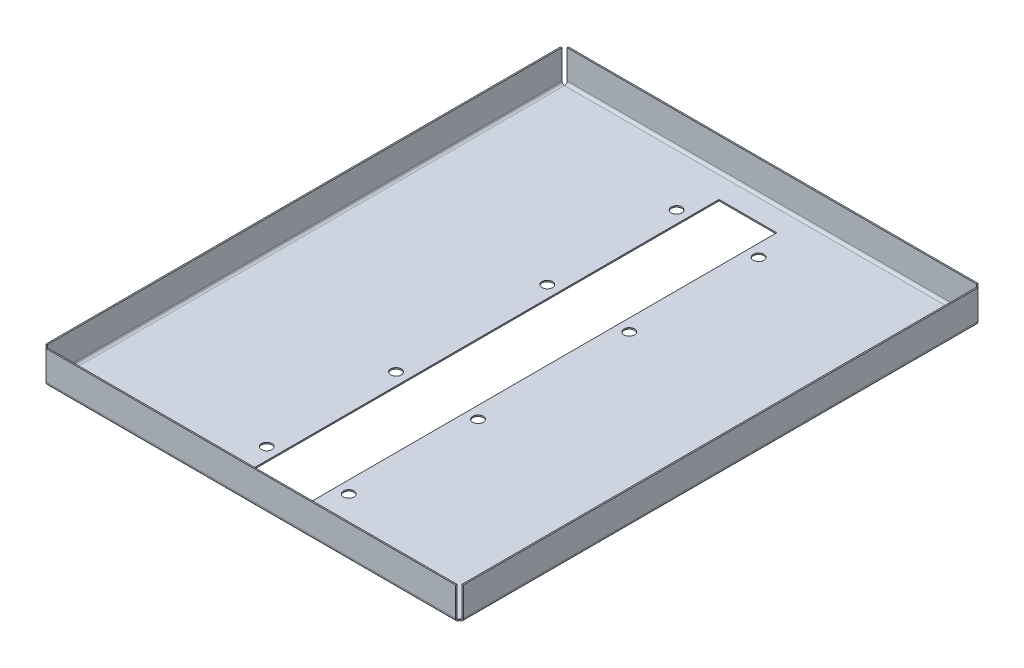
SolidWorks part; units mm, degrees
note: The reader was unsure of these and kept them because the rebuilt part matched: flange length of "Edge-Flange1", "Edge-Flange2", "Edge-Flange3", "Edge-Flange4".
ref_plane "Front Plane" through (0, 0, 0) normal (0, 0, 1) x (1, 0, 0)
ref_plane "Top Plane" through (0, 0, 0) normal (0, 1, 0) x (1, 0, 0)
ref_plane "Right Plane" through (0, 0, 0) normal (1, 0, 0) x (0, 0, -1)
sketch "Sketch1" plane through (0, 0, 0) normal (0, 1, 0) x (1, 0, 0)
  line L1 (0, 0) -> (156, 0)
  line L2 (0, 0) -> (0, -196)
  line L3 (0, -196) -> (156, -196)
  line L4 (156, 0) -> (156, -196)
base flange "Base-Flange1" sketch "Sketch1" thickness 0.5 reverse thickness direction no parameters "D1"=20
edge flange "Edge-Flange1" sketch "Sketch4" flange angle 90 flange length 12 flange position bend outside bend radius 1 thickness 0.5 parameters "D6"=10
sketch "Sketch4" plane through (0, 0, 0) normal (1, 0, 0) x (0, 0, -1)
  line L1 (0, 0) -> (-196, 0) construction
  line L2 (-196, 0) -> (-196, 12)
  line L3 (-196, 12) -> (0, 12)
  line L4 (0, 12) -> (0, 0)
  line L5 (0, 0) -> (-196, 0)
bend "EdgeBend1" bend radius 1 bend angle 90 parameters "D5"=1
edge flange "Edge-Flange2" sketch "Sketch7" flange angle 90 flange length 12 flange position bend outside bend radius 1 thickness 0.5 parameters "D6"=10
sketch "Sketch7" plane through (0, 0, 196) normal (0, 0, -1) x (-1, 0, 0)
  line L1 (0, 0) -> (-156, 0) construction
  line L2 (-156, 0) -> (-156, 12)
  line L3 (-156, 12) -> (0, 12)
  line L4 (0, 12) -> (0, 0)
  line L5 (0, 0) -> (-156, 0)
bend "EdgeBend2" bend radius 1 bend angle 90 parameters "D5"=2
edge flange "Edge-Flange3" sketch "Sketch10" flange angle 90 flange length 12 flange position bend outside bend radius 1 thickness 0.5 parameters "D6"=10
sketch "Sketch10" plane through (156, 0, 0) normal (-1, 0, 0) x (0, 0, 1)
  line L1 (196, 0) -> (0, 0) construction
  line L2 (0, 0) -> (0, 12)
  line L3 (0, 12) -> (196, 12)
  line L4 (196, 12) -> (196, 0)
  line L5 (196, 0) -> (0, 0)
bend "EdgeBend3" bend radius 1 bend angle 90 parameters "D5"=3
edge flange "Edge-Flange4" sketch "Sketch13" flange angle 90 flange length 12 flange position bend outside bend radius 1 thickness 0.5 parameters "D6"=10
sketch "Sketch13" plane through (0, 0, 0) normal (0, 0, 1) x (1, 0, 0)
  line L1 (156, 0) -> (0, 0) construction
  line L2 (0, 0) -> (0, 12)
  line L3 (0, 12) -> (156, 12)
  line L4 (156, 12) -> (156, 0)
  line L5 (156, 0) -> (0, 0)
bend "EdgeBend4" bend radius 1 bend angle 90 parameters "D5"=4
sketch "Sketch14" plane through (0, -0.5, 0) normal (0, -1, 0) x (1, 0, 0)
  line L0 (78, 132.2102) -> (78, 2.1064) construction
  line L2 (156, 98) -> (50.6638, 98) construction
  line L5 (89, 8.1446) -> (67, 8.1446)
  line L6 (89, 8.1446) -> (89, 188.1446)
  line L7 (89, 188.1446) -> (67, 188.1446)
  line L8 (67, 8.1446) -> (67, 188.1446)
  line L9 (89, 8.1446) -> (67, 188.1446) construction
  line L10 (89, 188.1446) -> (67, 8.1446) construction
  point P2 (78, 98.1446)
extrude "Cut-Extrude1" cut sketch "Sketch14" against normal blind 2 normal cut yes
sketch "Sketch15" plane through (0, 0, 0) normal (0, 1, 0) x (1, 0, 0)
  circle A0 centre (93.6217, -175.8052) radius 2
  circle A1 centre (62.3851, -175.8052) radius 2
  circle A2 centre (93.6217, -126.5523) radius 2
  circle A3 centre (62.3851, -126.5523) radius 2
  circle A4 centre (93.6217, -68.939) radius 2
  circle A5 centre (62.3851, -68.939) radius 2
  circle A6 centre (93.6217, -19.6862) radius 2
  circle A7 centre (62.3851, -19.6862) radius 2
extrude "Cut-Extrude2" cut sketch "Sketch15" against normal blind 2 normal cut yes
sketch "Bend-Lines1" [suppressed] plane through (0, 0, 0) normal (0, 1, 0) x (-1, 0, 0)
sketch "Bounding-Box1" [suppressed] plane through (0, 0, 0) normal (0, 1, 0) x (-1, 0, 0)
sheet metal parameters "Sheet-Metal(1)" thickness 0.5 parameters "D1"=20
flat pattern "Flat-Pattern(1)" [suppressed]
sketch "Bend-Lines2" plane through (0, 0, 0) normal (0, 1, 0) x (-1, 0, 0)
sketch "Bounding-Box2" [suppressed] plane through (0, 0, 0) normal (0, 1, 0) x (-1, 0, 0)
sheet metal parameters "Sheet-Metal(34)" thickness 0.5 parameters "D1"=20
flat pattern "Flat-Pattern(1)" [suppressed]
sketch "Bend-Lines2" plane through (0, 0, 0) normal (0, 1, 0) x (-1, 0, 0)
sketch "Bounding-Box2" [suppressed] plane through (0, 0, 0) normal (0, 1, 0) x (-1, 0, 0)
bend of the flat pattern "Flatten-<EdgeBend1>1"
sheet metal parameters "Sheet-Metal(35)" thickness 0.5 parameters "D1"=20
flat pattern "Flat-Pattern(1)" [suppressed]
sketch "Bend-Lines2" plane through (0, 0, 0) normal (0, 1, 0) x (-1, 0, 0)
sketch "Bounding-Box2" [suppressed] plane through (0, 0, 0) normal (0, 1, 0) x (-1, 0, 0)
bend of the flat pattern "Flatten-<EdgeBend1>1"
bend of the flat pattern "Flatten-<EdgeBend2>1"
sheet metal parameters "Sheet-Metal(36)" thickness 0.5 parameters "D1"=20
flat pattern "Flat-Pattern(1)" [suppressed]
sketch "Bend-Lines2" plane through (0, 0, 0) normal (0, 1, 0) x (-1, 0, 0)
sketch "Bounding-Box2" [suppressed] plane through (0, 0, 0) normal (0, 1, 0) x (-1, 0, 0)
bend of the flat pattern "Flatten-<EdgeBend1>1"
bend of the flat pattern "Flatten-<EdgeBend2>1"
bend of the flat pattern "Flatten-<EdgeBend3>1"
sheet metal parameters "Sheet-Metal(37)" thickness 0.5 parameters "D1"=20
flat pattern "Flat-Pattern(1)" [suppressed]
sketch "Bend-Lines2" plane through (0, 0, 0) normal (0, 1, 0) x (-1, 0, 0)
sketch "Bounding-Box2" [suppressed] plane through (0, 0, 0) normal (0, 1, 0) x (-1, 0, 0)
bend of the flat pattern "Flatten-<EdgeBend1>1"
bend of the flat pattern "Flatten-<EdgeBend2>1"
bend of the flat pattern "Flatten-<EdgeBend3>1"
bend of the flat pattern "Flatten-<EdgeBend4>1"
sheet metal parameters "Sheet-Metal(48)" thickness 0.5 parameters "D1"=20
flat pattern "Flat-Pattern(1)" [suppressed]
sketch "Bend-Lines2" plane through (0, 0, 0) normal (0, 1, 0) x (-1, 0, 0)
sketch "Bounding-Box2" [suppressed] plane through (0, 0, 0) normal (0, 1, 0) x (-1, 0, 0)
bend of the flat pattern "Flatten-<EdgeBend1>1"
bend of the flat pattern "Flatten-<EdgeBend2>1"
bend of the flat pattern "Flatten-<EdgeBend3>1"
bend of the flat pattern "Flatten-<EdgeBend4>1"
sheet metal parameters "Sheet-Metal(49)" thickness 0.5 parameters "D1"=20
flat pattern "Flat-Pattern(1)" [suppressed]
sketch "Bend-Lines2" plane through (0, 0, 0) normal (0, 1, 0) x (-1, 0, 0)
sketch "Bounding-Box2" [suppressed] plane through (0, 0, 0) normal (0, 1, 0) x (-1, 0, 0)
bend of the flat pattern "Flatten-<EdgeBend1>1"
bend of the flat pattern "Flatten-<EdgeBend2>1"
bend of the flat pattern "Flatten-<EdgeBend3>1"
bend of the flat pattern "Flatten-<EdgeBend4>1"
